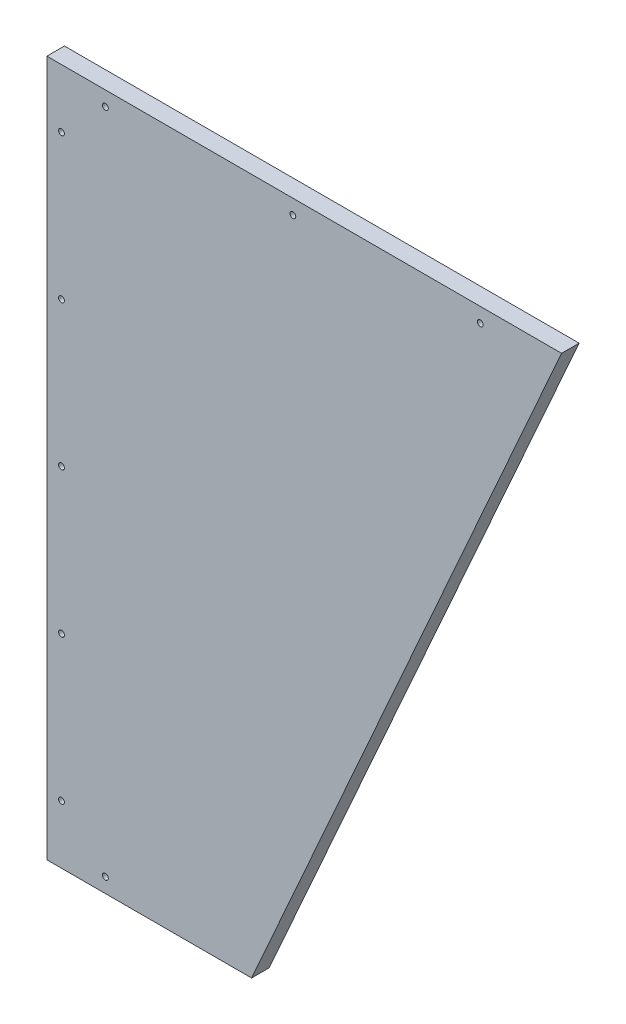
SolidWorks part; units mm, degrees
material "西洋杉"
ref_plane "正面" through (0, 0, 0) normal (0, 0, 1) x (1, 0, 0)
ref_plane "平面" through (0, 0, 0) normal (0, 1, 0) x (1, 0, 0)
ref_plane "右側面" through (0, 0, 0) normal (1, 0, 0) x (0, 0, -1)
sketch "ｽｹｯﾁ1" plane through (0, 0, 0) normal (0, 0, 1) x (1, 0, 0)
  line L0 (0, 297.5) -> (0, -297.5) construction
  line L1 (-220, 297.5) -> (220, 297.5)
  line L2 (-220, 297.5) -> (-220, -297.5)
  line L3 (-220, -297.5) -> (-45, -297.5)
  line L4 (220, 297.5) -> (-45, -297.5)
  line L5 (-220, 297.5) -> (-45, -297.5) construction
  line L6 (-220, -297.5) -> (220, 297.5) construction
  line L7 (-220, 0) -> (87.5, 0) construction
  point P0 (-106.7563, -87.5284)
  dimension "D1" = 595
  dimension "D2" = 440
  dimension "D3" = 175
extrude "ﾎﾞｽ - 押し出し1" add sketch "ｽｹｯﾁ1" along normal blind 15
sketch "ｽｹｯﾁ2" plane through (0, 0, 15) normal (0, 0, 1) x (1, 0, 0)
  line L0 (-207.5, 297.5) -> (-207.5, -297.5) construction
  line L1 (220, 297.5) -> (-220, 297.5) construction
  line L2 (-220, -297.5) -> (-45, -297.5) construction
  line L3 (-220, 297.5) -> (-220, -297.5) construction
  line L4 (-220, 285) -> (214.4328, 285) construction
  line L5 (-45, -297.5) -> (220, 297.5) construction
  circle A0 centre (-207.5, 247.5) radius 2.5
  circle A1 centre (-207.5, 123.75) radius 2.5
  circle A2 centre (-207.5, 0) radius 2.5
  circle A3 centre (-170, 285) radius 2.5
  circle A4 centre (-9.725, 285) radius 2.5
  circle A5 centre (150.55, 285) radius 2.5
  circle A6 centre (-207.5, -123.75) radius 2.5
  circle A7 centre (-207.5, -247.5) radius 2.5
  point P28 (0, 0)
  dimension "D2" = 5
  dimension "D7" = 5
  dimension "D1" = 12.5
  dimension "D3" = 50
  dimension "D5" = 12.5
  dimension "D6" = 434.4328
  dimension "D8" = 50
  dimension "D10" = 595
  dimension "D11" = 123.75
  dimension "D12" = 160.275
  dimension "D4" = 5
  dimension "D9" = 3
extrude "ｶｯﾄ - 押し出し1" cut sketch "ｽｹｯﾁ2" against normal through all contours A3 | A4 | A5
extrude "ｶｯﾄ - 押し出し2" cut sketch "ｽｹｯﾁ2<3>" against normal through all contours A0 | A1 | A2 | A6 | A7
sketch "ｽｹｯﾁ2<3>" plane through (0, 0, 15) normal (0, 0, 1) x (1, 0, 0) same geometry as "ｽｹｯﾁ2"
mirror "ﾐﾗｰ1" about plane through (0, 0, 0) normal (0, 1, 0) of "ｶｯﾄ - 押し出し1"
equation "\"D2@ｽｹｯﾁ1\"=925-485.00mm"
equation "\"D3@ｽｹｯﾁ1\"=925-750.00mm"
equation "\"D11@ｽｹｯﾁ2\"=(595-100)/4"
equation "\"D12@ｽｹｯﾁ2\"=(420.55-100)/2"
